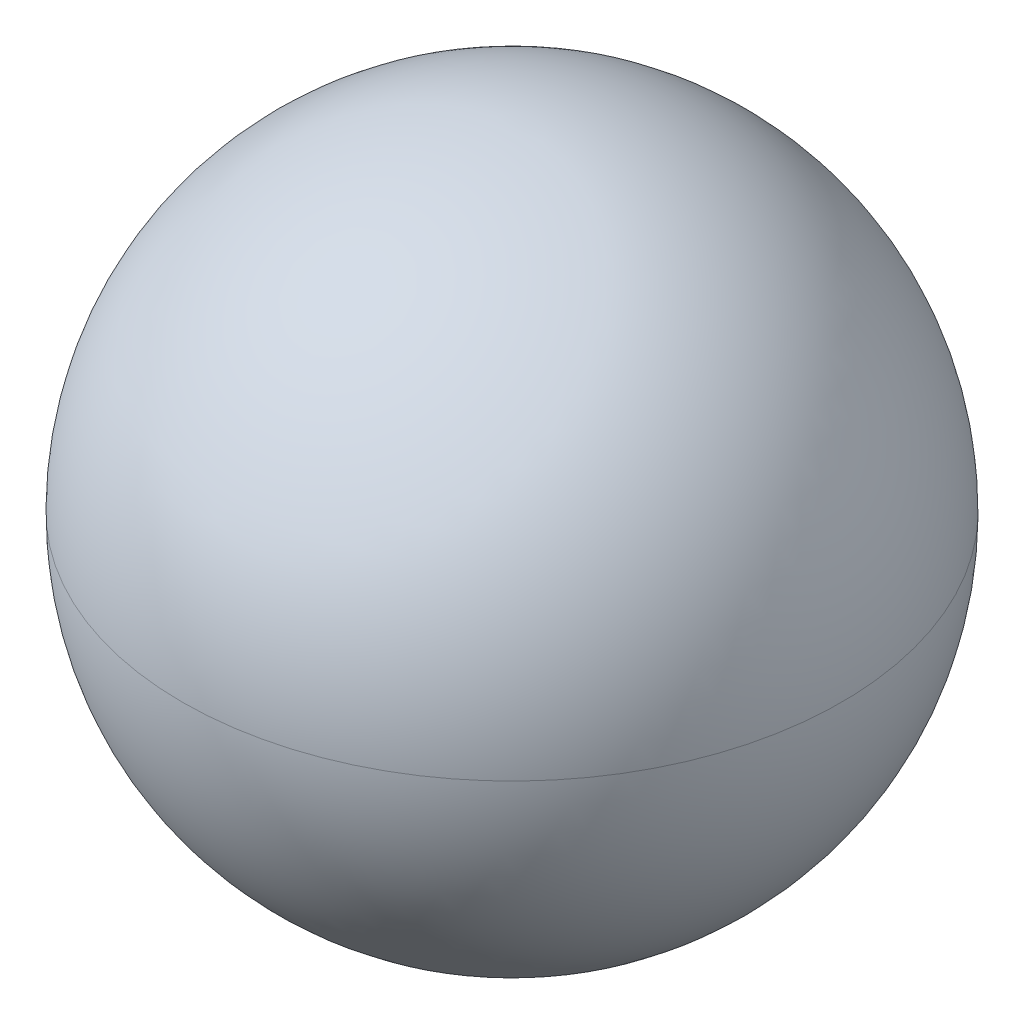
SolidWorks part; units mm, degrees
ref_plane "Front Plane" through (0, 0, 0) normal (0, 0, 1) x (1, 0, 0)
ref_plane "Top Plane" through (0, 0, 0) normal (0, 1, 0) x (1, 0, 0)
ref_plane "Right Plane" through (0, 0, 0) normal (1, 0, 0) x (0, 0, -1)
sketch "Sketch1" plane through (0, 0, 0) normal (0, 1, 0) x (1, 0, 0)
  circle A0 centre (0, 0) radius 304.8
  dimension "D1" = 609.6
extrude "Boss-Extrude1" add sketch "Sketch1" along normal blind 609.6
fillet "Fillet1" radius 304.8 2 edges at (0, 0, 304.8) (0, 609.6, 304.8)
shell "Shell2" thickness 3.175
